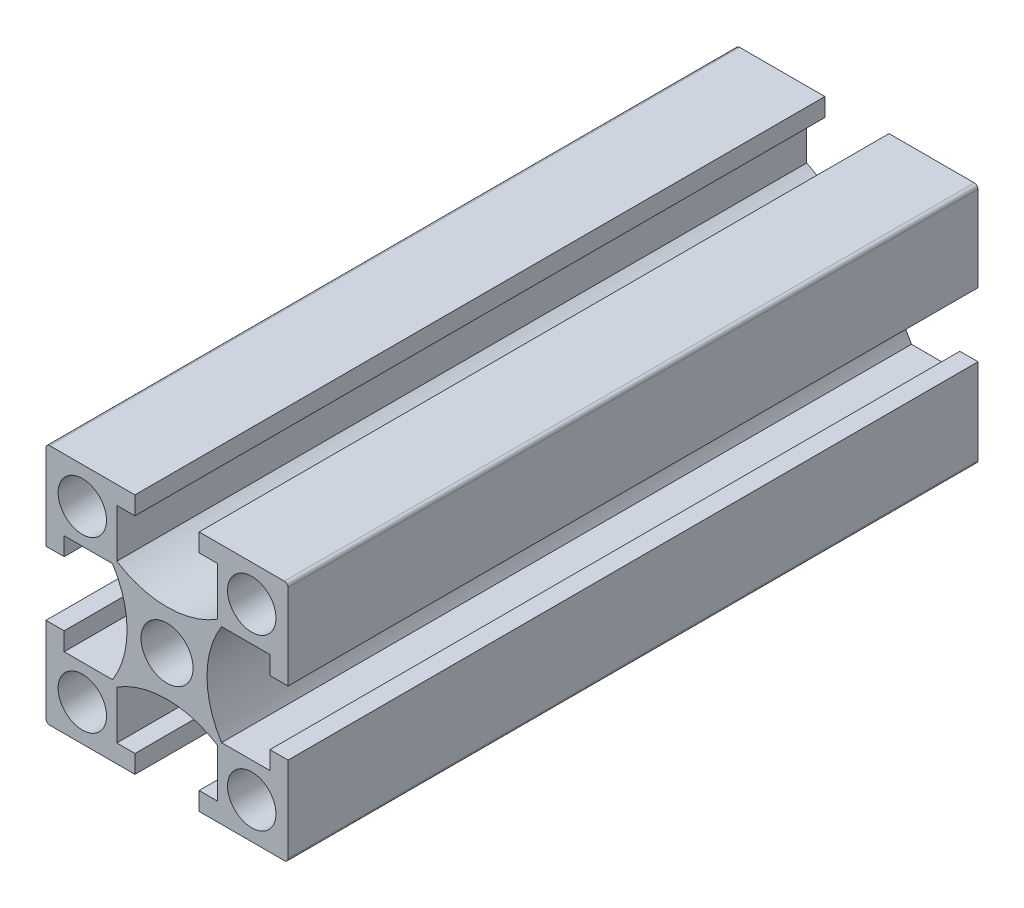
SolidWorks part; units mm, degrees
ref_plane "정면" through (0, 0, 0) normal (0, 0, 1) x (1, 0, 0)
ref_plane "윗면" through (0, 0, 0) normal (0, 1, 0) x (1, 0, 0)
ref_plane "우측면" through (0, 0, 0) normal (1, 0, 0) x (0, 0, -1)
sketch "스케치1" plane through (0, 0, 0) normal (0, 0, 1) x (1, 0, 0)
  line L0 (0, 32.0265) -> (0, -31.6588) construction
  line L1 (-10, 10) -> (-10, -10)
  line L2 (-10, 10) -> (10, 10)
  line L3 (-10, 2.65) -> (-8.5, 2.65)
  line L4 (13.6618, 0) -> (-11.6993, 0) construction
  line L5 (-8.5, 2.65) -> (-8.5, 4.15)
  line L6 (-8.5, 4.15) -> (-4.5032, 4.15)
  line L7 (-10, -2.65) -> (-8.5, -2.65)
  line L8 (-8.5, -2.65) -> (-8.5, -4.15)
  line L9 (-8.5, -4.15) -> (-4.5032, -4.15)
  line L10 (-10, -10) -> (10, -10)
  line L11 (10, 10) -> (10, -10)
  circle A0 centre (-7, 7) radius 2
  circle A1 centre (-7, -7) radius 2
  arc A2 (-4.5032, 4.15) -> (-4.5032, -4.15) centre (-11.0587, 0) cw
  circle A3 centre (0, 0) radius 2.15
  circle A4 centre (7, 7) radius 2
  circle A5 centre (7, -7) radius 2
  point P21 (-10, 0)
  point P23 (-3.3, 0)
  point P31 (0, -10)
  point P32 (0, 10)
  dimension "D3" = 4
  dimension "D9" = 6.7
  dimension "D10" = 4.3
  dimension "D11" = 7.7587
  dimension "D1" = 20
  dimension "D2" = 20
  dimension "D4" = 14
  dimension "D5" = 14
  dimension "D6" = 5.3
  dimension "D7" = 8.3
  dimension "D8" = 1.5
extrude "보스-돌출1" add sketch "스케치1" along normal blind 57 contours A0 | A4 | A3 | A5 | A1 | A2 L6 L5 L3 L1 L7 L8 L9 | L2 L11 L10 L1 region at (-6.6069, 0, 0) region at (-7, 7, 0) region at (-7, -7, 0) region at (0, 0, 0) region at (7, 7, 0) region at (7, -7, 0)
extrude "컷-돌출1" cut sketch "스케치1<3>" along normal up to next contours A2 L6 L5 L3 L1 L7 L8 L9 region at (-6.6069, 0, 0)
sketch "스케치1<3>" plane through (0, 0, 0) normal (0, 0, 1) x (1, 0, 0) same geometry as "스케치1"
pattern_circular "원형 패턴1" count 4 over 360 about axis through (0, 0, 57) along (0, 0, -1) of "컷-돌출1" reverse direction yes
fillet "필렛1" radius 0.3 4 edges at (10, -10, 28.5) (-10, -10, 28.5) (-10, 10, 28.5) (10, 10, 28.5)
sketch "스케치2" plane through (0, 0, 0) normal (1, 0, 0) x (0, 0, -1)
  line L0 (3.7612, 0) -> (-18.9549, 0) construction
  line L1 (0, -4.15) -> (0, 4.15) construction
  circle A0 centre (-19, 0) radius 2.5
  point P2 (0, 0)
  dimension "D1" = 5
  dimension "D2" = 19
extrude "컷-돌출2" cut sketch "스케치2" against normal through all both and the other way through all contours A0
